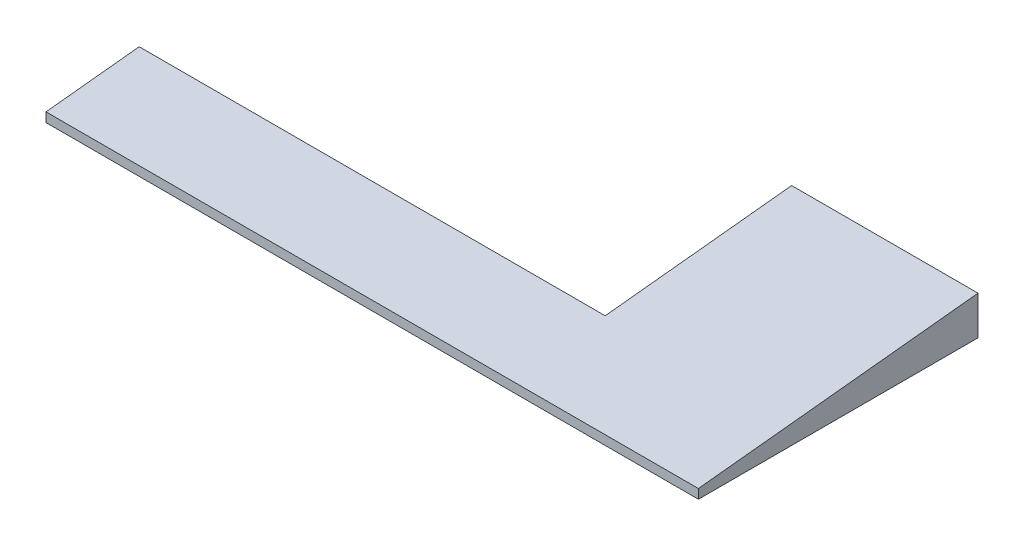
SolidWorks part; units mm, degrees
ref_plane "Front Plane" through (0, 0, 0) normal (0, 0, 1) x (1, 0, 0)
ref_plane "Top Plane" through (0, 0, 0) normal (0, 1, 0) x (1, 0, 0)
ref_plane "Right Plane" through (0, 0, 0) normal (1, 0, 0) x (0, 0, -1)
sketch "Sketch1" plane through (0, 0, 0) normal (0, 1, 0) x (1, 0, 0)
  line L1 (0, 0) -> (177.8, 0)
  line L2 (0, 0) -> (0, 25.4)
  line L3 (127, 76.2) -> (177.8, 76.2)
  line L4 (177.8, 0) -> (177.8, 76.2)
  line L7 (0, 25.4) -> (127, 25.4)
  line L8 (127, 76.2) -> (127, 25.4)
  point P8 (127, 50.8)
  dimension "D1" = 177.8
  dimension "D2" = 76.2
  dimension "D3" = 25.4
  dimension "D4" = 50.8
extrude "Boss-Extrude1" add sketch "Sketch1" along normal blind 15.24
chamfer "Chamfer1" distance 12.7 angle 84 1 edges at (88.9, 15.24, 0) first distance on face at (88.9, 7.62, 0)
